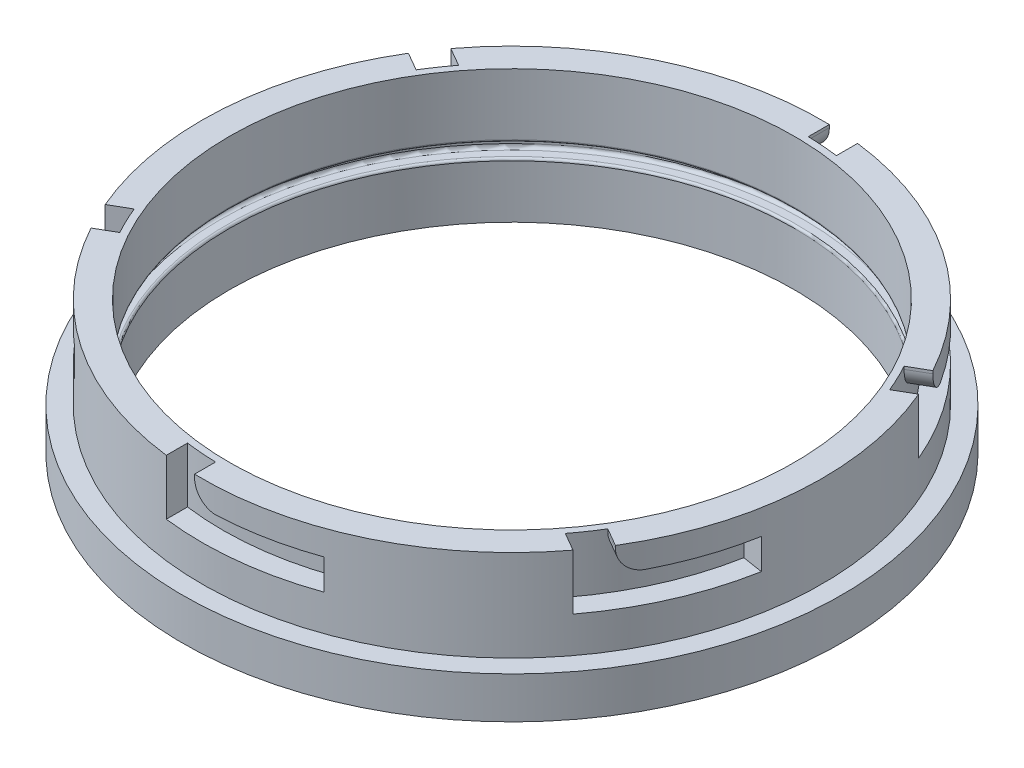
SolidWorks part; units mm, degrees
material "6061-T6 (SS)"
ref_plane "Front Plane" through (0, 0, 0) normal (0, 0, 1) x (1, 0, 0)
ref_plane "Top Plane" through (0, 0, 0) normal (0, 1, 0) x (1, 0, 0)
ref_plane "Right Plane" through (0, 0, 0) normal (1, 0, 0) x (0, 0, -1)
sketch "Sketch1" plane through (0, 0, 0) normal (0, 0, 1) x (1, 0, 0)
  line L0 (0, 60.758) -> (0, -61.3352) construction
  line L1 (71.12, 36.5125) -> (71.12, 15.5575)
  line L2 (71.12, 15.5575) -> (75.565, 15.5575)
  line L3 (75.565, 15.5575) -> (75.565, 6.0325)
  line L4 (75.565, 6.0325) -> (64.77, 6.0325)
  line L5 (64.77, 6.0325) -> (64.77, 18.7325)
  line L6 (64.77, 36.5125) -> (71.12, 36.5125)
  line L7 (64.77, 18.7325) -> (67.818, 18.7325)
  line L8 (67.818, 18.7325) -> (67.818, 21.9075)
  line L9 (67.818, 21.9075) -> (64.77, 21.9075)
  line L10 (64.77, 21.9075) -> (64.77, 36.5125)
  dimension "D1" = 6.35
  dimension "D2" = 9.525
  dimension "D3" = 30.48
  dimension "D4" = 71.12
  dimension "D5" = 75.565
  dimension "D6" = 3.048
  dimension "D7" = 12.7
  dimension "D8" = 15.875
revolve "Revolve1" add sketch "Sketch1" angle 360 about L0
sketch "Sketch2" plane through (0, 36.5125, 0) normal (0, 1, 0) x (1, 0, 0)
  line L0 (-8.6592, -70.5909) -> (-8.6592, -65.726)
  line L1 (-1.6742, -71.1003) -> (-1.6742, -66.2729)
  arc A0 (-1.6742, -71.1003) -> (-8.6592, -70.5909) centre (0, 0) cw
  circle A1 centre (0, 0) radius 71.12 construction
  arc A2 (-1.6742, -66.2729) -> (-8.6592, -65.726) centre (0, 0) cw
  dimension "D1" = 4.826
  dimension "D2" = 6.985
  dimension "D3" = 6.985
extrude "Cut-Extrude1" cut sketch "Sketch2" against normal blind 12.7
sketch "Sketch10" plane through (-1.6742, 0, 0) normal (-1, 0, 0) x (0, 0, 1)
  line L0 (66.2729, 23.8125) -> (66.2729, 30.7975)
  line L1 (66.2729, 23.8125) -> (66.2729, 36.5125) construction
  line L2 (66.2729, 30.7975) -> (71.1003, 30.7975)
  line L3 (71.1003, 23.8125) -> (71.1003, 36.5125) construction
  line L4 (71.1003, 30.7975) -> (71.1003, 23.8125)
  line L5 (71.1003, 23.8125) -> (66.2729, 23.8125)
  dimension "D1" = 6.985
ref_axis "Axis1" through (0, 6.0325, 0) along (0, 1, 0)
sketch "Sketch21" plane through (0, 23.8125, 0) normal (0, 1, 0) x (1, 0, 0)
  line L0 (-1.6742, -71.1003) -> (-1.6742, -66.2729) construction
  arc A0 (-1.6742, -73.5126) -> (73.4476, -3.5158) centre (0, 0) ccw
sketch "Sketch22" plane through (0, 23.8125, 0) normal (0, 1, 0) x (1, 0, 0)
  circle A1 centre (0, 0) radius 73.5317
sketch "Sketch23" plane through (0, 23.8125, 0) normal (0, 1, 0) x (1, 0, 0)
  arc A0 (-1.6742, -71.1003) -> (23.922, -66.9761) centre (0, 0) ccw
sweep "Cut-Sweep2" cut profiles "Sketch10" path "Sketch23"
fillet "Fillet1" radius 5.08 1 edges at (-1.6742, 30.7975, 68.6866)
pattern_circular "CirPattern1" count 6 over 360 about axis through (0, 60.758, 0) along (0, 1, 0) of "Fillet1", "Cut-Extrude1", "Cut-Sweep2" reverse direction yes
fillet "Fillet2" radius 0.762 2 edges at (-67.818, 21.9075, 0) (-67.818, 18.7325, 0)
fillet "Fillet3" radius 0.508 2 edges at (-64.77, 18.7325, 0) (-64.77, 21.9075, 0)
sketch "Sketch24" plane through (0, 6.0325, 0) normal (0, -1, 0) x (1, 0, 0)
  line L0 (-2.0961, 67.1054) -> (-1.1566, 67.1033)
  line L1 (-1.6263, 67.1043) -> (-1.6325, 64.2837) construction
  line L2 (-3.1931, 64.513) -> (-0.071, 64.5062)
  spline S0 degree 3 poles (-2.0961, 67.1054) (-2.1672, 66.9295) (-2.2659, 66.6682) (-2.4002, 66.2739) (-2.4676, 66.0573) (-2.5063, 65.9255) knots 0 0 0 0 0.455486 0.670301 1 1 1 1
  spline S1 degree 3 poles (-2.5063, 65.9255) (-2.5773, 65.6449) (-2.6547, 65.2845) (-2.7636, 64.9081) (-2.7851, 64.7854) (-2.8051, 64.7157) (-2.8445, 64.6485) (-2.9065, 64.5845) (-3.0202, 64.5178) (-3.1269, 64.5162) (-3.1931, 64.513) knots 0 0 0 0 0.50758 0.647219 0.68628 0.726157 0.773713 0.821128 0.881401 1 1 1 1
  spline S2 degree 3 poles (-1.1566, 67.1033) (-1.0863, 66.9271) (-0.9887, 66.6654) (-0.8561, 66.2705) (-0.7897, 66.0536) (-0.7516, 65.9217) knots 0 0 0 0 0.455486 0.670301 1 1 1 1
  spline S3 degree 3 poles (-0.7516, 65.9217) (-0.6962, 65.7094) (-0.6454, 65.4407) (-0.5548, 65.1173) (-0.5157, 64.9486) (-0.4854, 64.8115) (-0.4614, 64.7227) (-0.4366, 64.6731) (-0.4076, 64.6316) (-0.3644, 64.5877) (-0.3091, 64.5493) (-0.2095, 64.5089) (-0.1255, 64.5109) (-0.071, 64.5062) knots 0 0 0 0 0.384807 0.478666 0.588978 0.688379 0.725395 0.749588 0.785292 0.813657 0.857185 0.902571 1 1 1 1
